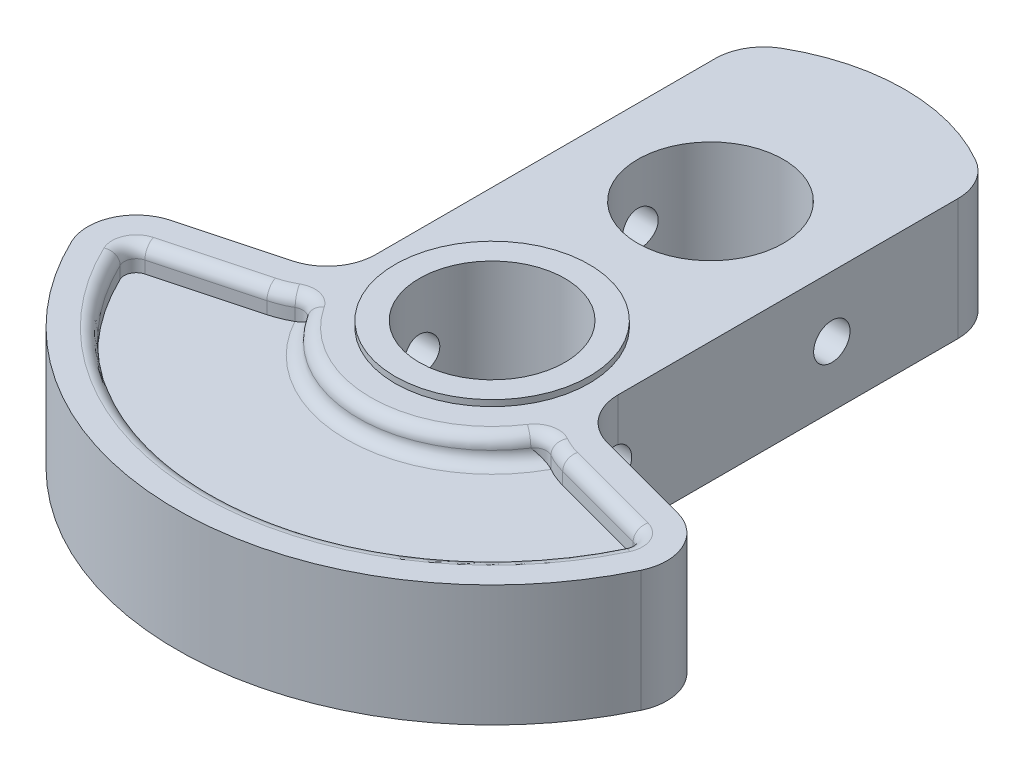
SolidWorks part; units mm, degrees
ref_plane "Front Plane" through (0, 0, 0) normal (0, 0, 1) x (1, 0, 0)
ref_plane "Top Plane" through (0, 0, 0) normal (0, 1, 0) x (1, 0, 0)
ref_plane "Right Plane" through (0, 0, 0) normal (1, 0, 0) x (0, 0, -1)
sketch "Sketch1" plane through (0, 0, 0) normal (0, 1, 0) x (1, 0, 0)
  line L0 (0, 34) -> (0, -20.708) construction
  line L1 (-10, 30.49) -> (-10, -2.6795)
  line L2 (10, 30.49) -> (10, -2.6795)
  line L3 (0, 0) -> (-25.1141, -6.7293) construction
  line L4 (0, 0) -> (25.1141, -6.7293) construction
  line L5 (-10, 39.1858) -> (-10, -20.708) construction
  line L6 (10, 39.1858) -> (10, -20.708) construction
  line L7 (-25.1141, -6.7293) -> (-10, -2.6795)
  line L8 (0, 39.1858) -> (0, -20.708) construction
  line L9 (10, -2.6795) -> (25.1141, -6.7293)
  arc A0 (10, 30.49) -> (-10, 30.49) centre (0, 18) ccw
  arc A2 (-25.1141, -6.7293) -> (25.1141, -6.7293) centre (0, 0) ccw
  point P9 (11.117, -1.4704)
  point P17 (-29.7606, 2.0326)
  point P18 (-24.7745, -6.6383)
  dimension "D2" = 32
  dimension "D5" = 26
  dimension "D1" = 18
  dimension "D6" = 75
  dimension "D7" = 75
  dimension "D3" = 10
  dimension "D4" = 10
extrude "Boss-Extrude1" add sketch "Sketch1" along normal mid plane 10
fillet "Fillet1" radius 4 6 edges at (25.1141, 0, 6.7293) (10, 0, -30.49) (-10, 0, -30.49) (-10, 0, 2.6795) (-25.1141, 0, 6.7293) (10, 0, 2.6795)
sketch "Sketch3" plane through (0, 5, 0) normal (0, 1, 0) x (1, 0, 0)
  circle A0 centre (0, 0) radius 8
  dimension "D1" = 16
extrude "Boss-Extrude2" add sketch "Sketch3" along normal mid plane 1
sketch "Sketch4" plane through (0, -5, 0) normal (0, -1, 0) x (1, 0, 0)
  circle A0 centre (0, -18) radius 8
  point P5 (-3.3052, -8.973)
  dimension "D1" = 16
  dimension "D2" = 18
extrude "Boss-Extrude3" add sketch "Sketch4" along normal mid plane 1
sketch "Sketch5" plane through (0, 5.5, 0) normal (0, 1, 0) x (1, 0, 0)
  circle A0 centre (0, 0) radius 6
  circle A1 centre (0, 18) radius 6
  dimension "D1" = 12
  dimension "D2" = 12
extrude "Cut-Extrude2" cut sketch "Sketch5" against normal through all
sketch "Sketch6" plane through (0, -5, 0) normal (0, -1, 0) x (1, 0, 0)
  line L6 (20.1197, 8.4969) -> (12.1883, 6.3717)
  line L7 (-12.1883, 6.3717) -> (-20.1197, 8.4969)
  line L8 (20.1197, 8.4969) -> (12.1883, 6.3717)
  line L9 (-12.1883, 6.3717) -> (-20.1197, 8.4969)
  arc A2 (-23.472, 11.1833) -> (-20.8962, 5.5991) centre (-19.8609, 9.4628) ccw construction
  arc A10 (9.7202, 5.1495) -> (-9.7202, 5.1495) centre (0, 0) ccw
  arc A15 (12.1883, 6.3717) -> (7, -0.3898) centre (14, -0.3898) ccw
  arc A16 (-7, -0.3898) -> (-12.1883, 6.3717) centre (-14, -0.3898) ccw
  arc A17 (20.1197, 8.4969) -> (20.7637, 9.8929) centre (19.8609, 9.4628) ccw
  arc A18 (-20.7637, 9.8929) -> (-20.1197, 8.4969) centre (-19.8609, 9.4628) ccw
  arc A19 (20.7637, 9.8929) -> (-20.7637, 9.8929) centre (0, 0) ccw
  arc A20 (12.1883, 6.3717) -> (9.7202, 5.1495) centre (14, -0.3898) ccw
  arc A21 (-9.7202, 5.1495) -> (-12.1883, 6.3717) centre (-14, -0.3898) ccw
  arc A22 (20.1197, 8.4969) -> (20.7637, 9.8929) centre (19.8609, 9.4628) ccw
  arc A23 (-20.7637, 9.8929) -> (-20.1197, 8.4969) centre (-19.8609, 9.4628) ccw
  arc A24 (20.7637, 9.8929) -> (-20.7637, 9.8929) centre (0, 0) ccw
  point P0 (0, 0)
  dimension "D2" = 11
  dimension "D3" = 3
  dimension "D1" = 3
extrude "Cut-Extrude3" cut sketch "Sketch6" against normal blind 2
fillet "Fillet4" radius 1 11 edges at (0, -5, 23) (-20.7689, -5, 9.044) (20.7689, -5, 9.044) (-16.154, -5, 7.4343) (16.154, -5, 7.4343) (-10.8936, -5, 5.8831) (10.8936, -5, 5.8831) (-9.7202, -4, 5.1495) (0, -3, 11) (9.7202, -4, 5.1495) (0, -5, 11)
mirror "Mirror1" about plane through (0, 0, 0) normal (0, 1, 0) of "Fillet4", "Cut-Extrude3"
sketch "Sketch7" plane through (0, 0, 0) normal (1, 0, 0) x (0, 0, -1)
  circle A0 centre (0, 0) radius 1.5
  circle A1 centre (18, 0) radius 1.5
  dimension "D1" = 18
extrude "Cut-Extrude4" cut sketch "Sketch7" against normal through all both and the other way through all
